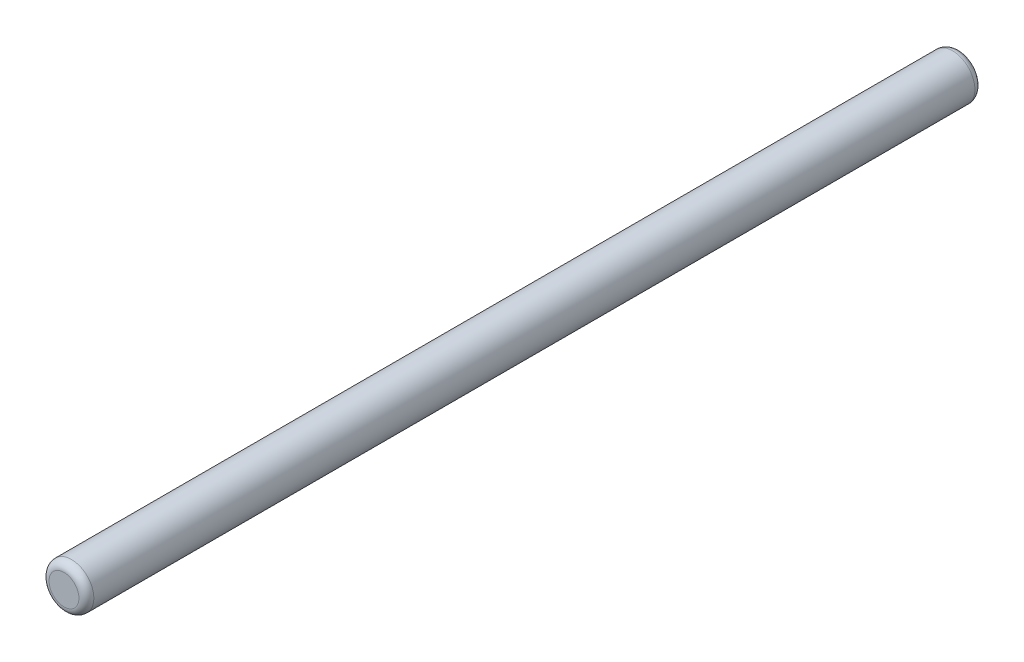
SolidWorks part; units mm, degrees
ref_plane "Ebene vorne" through (0, 0, 0) normal (0, 0, 1) x (1, 0, 0)
ref_plane "Ebene oben" through (0, 0, 0) normal (0, 1, 0) x (1, 0, 0)
ref_plane "Ebene rechts" through (0, 0, 0) normal (1, 0, 0) x (0, 0, -1)
sketch "Skizze1" plane through (0, 0, 0) normal (0, 0, 1) x (1, 0, 0)
  circle A0 centre (0, 0) radius 3
  dimension "D1" = 6
extrude "Bolzen" add sketch "Skizze1" along normal blind 120
fillet "Verrundung1" radius 1 2 edges at (3, 0, 0) (3, 0, 120)
